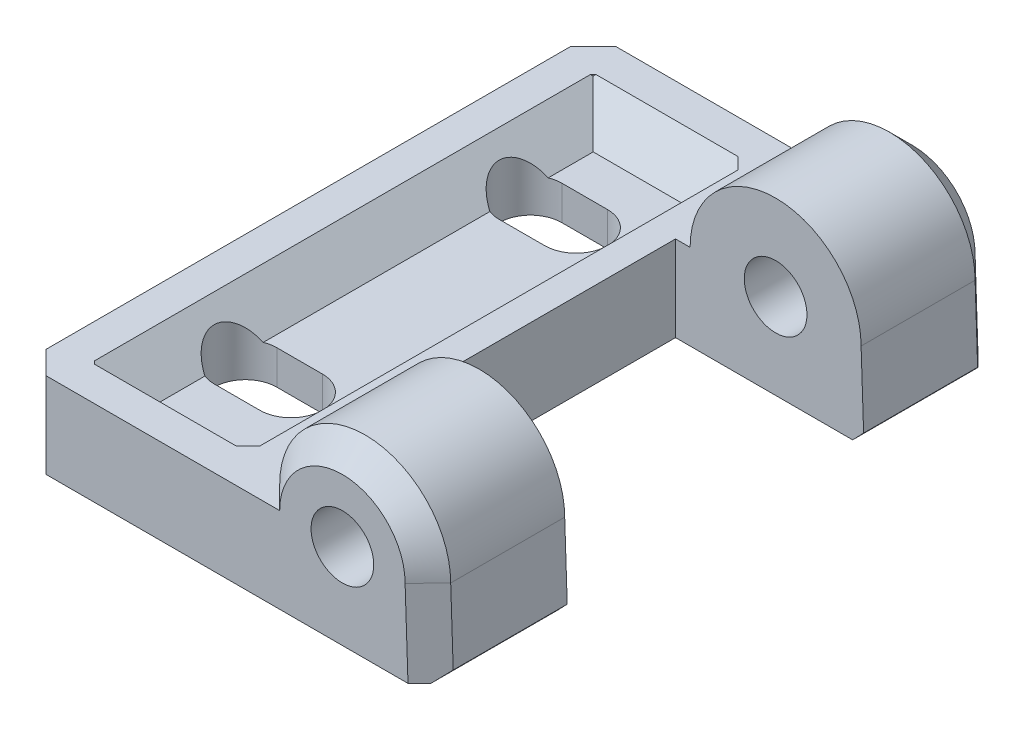
SolidWorks part; units mm, degrees
ref_plane "Front Plane" through (0, 0, 0) normal (0, 0, 1) x (1, 0, 0)
ref_plane "Top Plane" through (0, 0, 0) normal (0, 1, 0) x (1, 0, 0)
ref_plane "Right Plane" through (0, 0, 0) normal (1, 0, 0) x (0, 0, -1)
sketch "contour" plane through (0, 0, 0) normal (0, 0, 1) x (1, 0, 0)
  line L0 (7.5, 0) -> (7.7213, -6.5006)
  line L1 (-7.5, -0.0001) -> (-28, -0.0001)
  line L2 (6.7554, -7.5) -> (0, -7.5)
  line L3 (0, -7.5) -> (-28, -7.5)
  line L4 (-28, -0.0001) -> (-28, -7.5)
  line L5 (7.7213, -6.5006) -> (6.7554, -7.5)
  arc A0 (7.5, 0) -> (-7.5, -0.0001) centre (0, 0) ccw
  point P6 (7.7554, -7.5)
  dimension "D2" = 15
  dimension "D3" = 28
extrude "Boss-Extrude1" add sketch "contour" along normal mid plane 50
sketch "Sketch6" plane through (0, -7.5, 0) normal (0, -1, 0) x (1, 0, 0)
  line L0 (-28, 25) -> (-28, -25) construction
  line L1 (-28, 25) -> (6.7554, 25) construction
  line L2 (-21, 12.5) -> (-17, 12.5) construction
  line L3 (-21, 15.25) -> (-17, 15.25)
  line L4 (-21, 9.75) -> (-17, 9.75)
  line L5 (-21, -12.5) -> (-17, -12.5) construction
  line L6 (-21, -9.75) -> (-17, -9.75)
  line L7 (-21, -15.25) -> (-17, -15.25)
  circle A0 centre (-19, 12.5) radius 2.75 construction
  circle A1 centre (-19, -12.5) radius 2.75 construction
  arc A2 (-21, 15.25) -> (-21, 9.75) centre (-21, 12.5) ccw
  arc A3 (-17, 9.75) -> (-17, 15.25) centre (-17, 12.5) ccw
  arc A4 (-21, -9.75) -> (-21, -15.25) centre (-21, -12.5) ccw
  arc A5 (-17, -15.25) -> (-17, -9.75) centre (-17, -12.5) ccw
  point P10 (-19, 12.5)
  point P16 (-19, -12.5)
  dimension "D1" = 5.5
  dimension "D2" = 9
  dimension "D5" = 4
  dimension "D3" = 12.5
  dimension "D4" = 25
extrude "mount-holes" cut sketch "Sketch6" against normal through all
sketch "Sketch7" plane through (0, -7.5, 0) normal (0, -1, 0) x (1, 0, 0)
  line L1 (7.7213, 13) -> (-8.7787, 13)
  line L2 (7.7213, 13) -> (7.7213, -13)
  line L3 (7.7213, -13) -> (-8.7787, -13)
  line L4 (-8.7787, 13) -> (-8.7787, -13)
  line L5 (-7.5, -25) -> (7.5, -25) construction
  line L6 (7.5, 25) -> (-7.5, 25) construction
  line L7 (7.7213, 25) -> (7.7213, -25) construction
  dimension "D1" = 12
  dimension "D2" = 12
  dimension "D3" = 16.5
extrude "cut-part" cut sketch "Sketch7" against normal blind 20
sketch "axis" plane through (0, 0, 0) normal (0, 0, 1) x (1, 0, 0)
  circle A0 centre (0, 0) radius 2.75
  dimension "D1" = 5.5
extrude "Cut-Extrude3" cut sketch "axis" against normal mid plane 60
sketch "Sketch9" plane through (0, -7.5, 0) normal (0, -1, 0) x (1, 0, 0)
  line L17 (-17, 18.75) -> (-21, 18.75)
  line L18 (-21, 6.25) -> (-17, 6.25)
  line L19 (-17, 18.75) -> (-21, 18.75)
  line L20 (-21, 6.25) -> (-17, 6.25)
  line L23 (-21, -18.75) -> (-17, -18.75)
  line L24 (-17, -6.25) -> (-21, -6.25)
  line L25 (-21, -18.75) -> (-17, -18.75)
  line L26 (-17, -6.25) -> (-21, -6.25)
  arc A8 (-21, 18.75) -> (-21, 6.25) centre (-21, 12.5) ccw
  arc A9 (-17, 6.25) -> (-17, 18.75) centre (-17, 12.5) ccw
  arc A10 (-21, 18.75) -> (-21, 6.25) centre (-21, 12.5) ccw
  arc A11 (-17, 6.25) -> (-17, 18.75) centre (-17, 12.5) ccw
  arc A14 (-21, -6.25) -> (-21, -18.75) centre (-21, -12.5) ccw
  arc A15 (-17, -18.75) -> (-17, -6.25) centre (-17, -12.5) ccw
  arc A16 (-21, -6.25) -> (-21, -18.75) centre (-21, -12.5) ccw
  arc A17 (-17, -18.75) -> (-17, -6.25) centre (-17, -12.5) ccw
  dimension "D1" = 3.5
  dimension "D2" = 3.5
extrude "Cut-Extrude4" cut sketch "Sketch9" against normal blind 1.5
chamfer "Chamfer1" distance 2 angle 45 6 edges at (7.6107, -3.2503, -25) (7.6107, -3.2503, 25) (-28, -3.75, -25) (-28, -3.75, 25) (0, 7.5, -25) (0, 7.5, 25)
sketch "Sketch10" plane through (0, -0.0001, 0) normal (0, 1, 0) x (1, 0, 0)
  line L12 (-11.2787, 21) -> (-11.2787, -21)
  line L13 (-12.2787, 22) -> (-11.2787, 21)
  line L14 (-11.2787, -21) -> (-12.2787, -22)
  line L34 (-12.2787, 22) -> (-24.7574, 22)
  line L35 (-24.7574, 22) -> (-25, 21.7574)
  line L36 (-25, 21.7574) -> (-25, -21.7574)
  line L37 (-25, -21.7574) -> (-24.7574, -22)
  line L38 (-24.7574, -22) -> (-12.2787, -22)
  point P0 (-11.2787, 22)
  point P4 (-11.2787, -22)
extrude "Cut-Extrude5" cut sketch "Sketch10" against normal blind 3
chamfer "Chamfer2" distance 3 angle 45 4 edges at (-18.518, -3.0001, 22) (-25, -3.0001, 0) (-18.518, -3.0001, -22) (-11.2787, -3.0001, 0)
